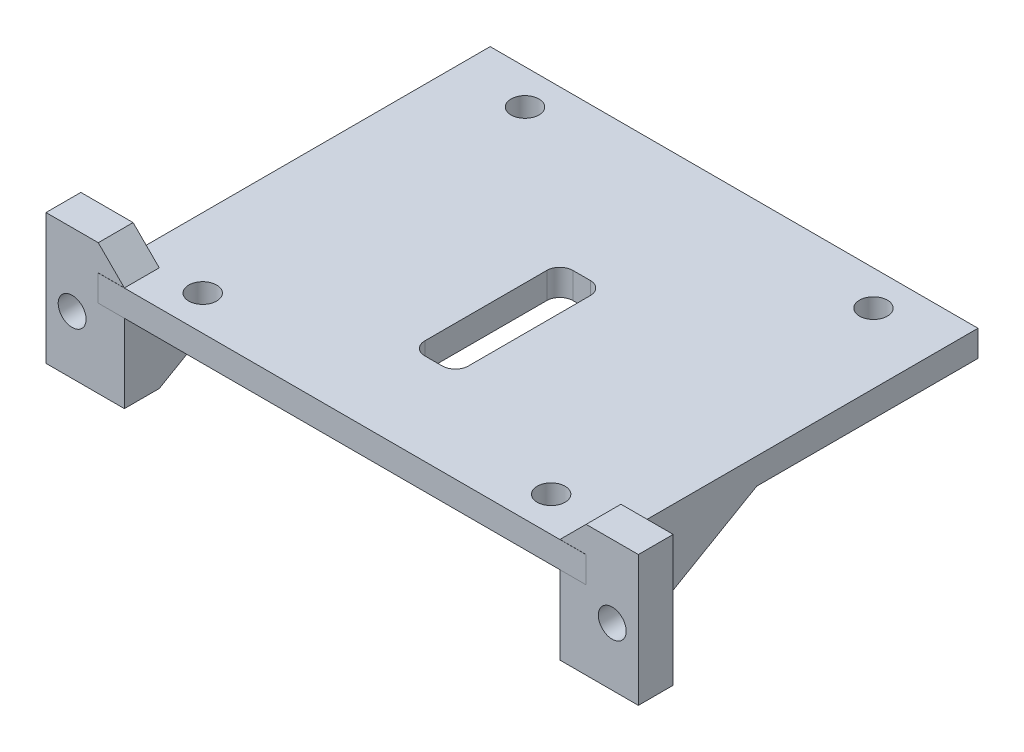
SolidWorks part; units mm, degrees
ref_plane "前视基准面" through (0, 0, 0) normal (0, 0, 1) x (1, 0, 0)
ref_plane "上视基准面" through (0, 0, 0) normal (0, 1, 0) x (1, 0, 0)
ref_plane "右视基准面" through (0, 0, 0) normal (1, 0, 0) x (0, 0, -1)
sketch "草图1" plane through (0, 0, 0) normal (0, 1, 0) x (1, 0, 0)
  line L1 (0, 0) -> (56, 0)
  line L2 (0, 0) -> (0, 45)
  line L3 (0, 45) -> (56, 45)
  line L4 (56, 0) -> (56, 45)
  dimension "D1" = 45
  dimension "D2" = 56
extrude "凸台-拉伸1" add sketch "草图1" along normal blind 3
sketch "草图2" plane through (0, 0, 0) normal (-1, 0, 0) x (0, 0, 1)
  line L0 (-0.013, 6) -> (-4.013, 6)
  line L1 (-4.013, 6) -> (-4.013, -9)
  line L2 (-4.013, -9) -> (-0.013, -9)
  line L3 (-0.013, -9) -> (-0.013, 6)
  line L4 (-45, 3) -> (0, 3) construction
  line L5 (-45, 0) -> (0, 0) construction
  dimension "D1" = 3
  dimension "D2" = 9
  dimension "D3" = 4
extrude "凸台-拉伸2" add sketch "草图2" along normal blind 6
sketch "草图3" plane through (56, 0, 0) normal (1, 0, 0) x (0, 0, -1)
  line L0 (0.013, 6) -> (0.013, -9)
  line L1 (0.013, -9) -> (4.013, -9)
  line L2 (4.013, -9) -> (4.013, 6)
  line L3 (4.013, 6) -> (0.013, 6)
extrude "凸台-拉伸3" add sketch "草图3" along normal blind 6
sketch "草图4" plane through (56, 0, 0) normal (-1, 0, 0) x (0, 0, 1)
  line L0 (-4.013, -9) -> (-19.6015, 0)
  line L1 (-4.013, 0) -> (-45, 0) construction
  line L2 (-19.6015, 0) -> (-0.013, 0)
  line L3 (-0.013, 0) -> (-0.013, -9)
  line L4 (-0.013, -9) -> (-4.013, -9)
  dimension "D1" = 30
extrude "凸台-拉伸4" add sketch "草图4" along normal blind 3
sketch "草图5" plane through (0, 0, 0) normal (1, 0, 0) x (0, 0, -1)
  line L0 (0.013, 0.3045) -> (0.013, -9)
  line L1 (0.013, -9) -> (4.013, -9)
  line L2 (4.013, -9) -> (19.6015, 0)
  line L3 (45, 0) -> (4.013, 0) construction
  line L4 (19.6015, 0) -> (0, 0)
  line M3 (4.013, -9) -> (4.013, 0)
  line M4 (4.013, 0) -> (0.013, 0)
  line M5 (0.013, 0) -> (0.013, -9)
  line M6 (0.013, -9) -> (4.013, -9)
  dimension "D1" = 30
extrude "凸台-拉伸5" add sketch "草图5" along normal blind 3 contours L2 L4 M3 | M6 M3 M4 M5 region at (0, -4.5, -2.013) region at (0, -3, -9.2092)
chamfer "倒角1" distance 3 angle 45 2 edges at (0, 3, -2.013) (56, 3, -2.013)
sketch "草图6" plane through (0, 0, -4.013) normal (0, 0, -1) x (-1, 0, 0)
  line L0 (-59, -2.3233) -> (3, -2.3233) construction
  line L1 (-62, -9) -> (-62, 6) construction
  line L2 (6, 6) -> (6, -9) construction
  circle A0 centre (3, -2.3233) radius 1.6
  circle A1 centre (-59, -2.3233) radius 1.6
  dimension "D1" = 3
  dimension "D2" = 3
extrude "切除-拉伸1" cut sketch "草图6" against normal blind 4
sketch "草图7" plane through (0, 3, 0) normal (0, 1, 0) x (1, 0, 0)
  line L0 (28, 49.7957) -> (28, -5.721) construction
  line L1 (8, 41) -> (8, 4)
  line L2 (0, 0) -> (56, 0) construction
  line L3 (0, 45) -> (0, 4.013) construction
  line L4 (48, 41) -> (48, 4)
  circle A0 centre (8, 41) radius 1.6
  circle A1 centre (8, 4) radius 1.6
  circle A2 centre (48, 4) radius 1.6
  circle A3 centre (48, 41) radius 1.6
  dimension "D1" = 37
  dimension "D2" = 4
  dimension "D3" = 8
extrude "切除-拉伸2" cut sketch "草图7" against normal blind 3 contours A3 | A2 | A0 | A1 region at (49.0994, 3, -5.0994) region at (46.9006, 3, -42.0994)
sketch "草图8" plane through (0, 0, 0) normal (0, -1, 0) x (1, 0, 0)
  line L0 (24, -45) -> (32, -45)
  line L1 (56, -45) -> (0, -45) construction
  line L2 (32, -45) -> (32, -42)
  line L3 (32, -42) -> (24, -42)
  line L4 (24, -42) -> (24, -45)
  line L5 (28, 5.34) -> (28, -50.6665) construction
  line L6 (0, -45) -> (0, -19.6015) construction
  point P10 (32, -43.5)
  dimension "D1" = 28
  dimension "D2" = 3
  dimension "D3" = 8
  dimension "D4" = 4
extrude "凸台-拉伸6" add sketch "草图8" along normal blind 9
sketch "草图9" plane through (32, 0, 0) normal (1, 0, 0) x (0, 0, -1)
  line L0 (45, 0) -> (29.1467, 0)
  line L1 (29.1467, 0) -> (42, -9)
  line L2 (42, -9) -> (45, -9)
  line L3 (45, -9) -> (45, 0)
  dimension "D1" = 35
extrude "凸台-拉伸7" add sketch "草图9" along normal blind 3
sketch "草图10" plane through (24, 0, 0) normal (-1, 0, 0) x (0, 0, 1)
  line L0 (-45, 0) -> (-45, -9)
  line L1 (-45, -9) -> (-42, -9)
  line L2 (-42, -9) -> (-29.1467, 0)
  line L3 (-29.1467, 0) -> (-45, 0)
extrude "凸台-拉伸8" add sketch "草图10" along normal blind 3
sketch "草图11" plane through (0, 0, -42) normal (0, 0, 1) x (1, 0, 0)
  line L0 (24, -9) -> (24, 0) construction
  line L1 (32, -9) -> (24, -9) construction
  circle A0 centre (28, -4.5) radius 1.6
  dimension "D1" = 4
  dimension "D2" = 4.5
extrude "切除-拉伸3" cut sketch "草图11" against normal blind 3
sketch "草图12" plane through (0, 3, 0) normal (0, 1, 0) x (1, 0, 0)
  line L0 (28, 49.4691) -> (28, -3.816) construction
  line L1 (25.5, 27.5) -> (25.5, 10.5)
  line L2 (25.5, 10.5) -> (30.5, 10.5)
  line L3 (30.5, 10.5) -> (30.5, 27.5)
  line L4 (30.5, 27.5) -> (25.5, 27.5)
  line L5 (0, 45) -> (0, 4.013) construction
  line L6 (-5.009, 22.5) -> (59.3487, 22.5) construction
  line L7 (0, 0) -> (56, 0) construction
  dimension "D1" = 28
  dimension "D2" = 2.5
  dimension "D3" = 2.5
  dimension "D4" = 22.5
  dimension "D5" = 5
  dimension "D6" = 12
extrude "切除-拉伸4" cut sketch "草图12" against normal blind 3
fillet "圆角1" radius 1.5 4 edges at (30.5, 1.5, -10.5) (25.5, 1.5, -10.5) (25.5, 1.5, -27.5) (30.5, 1.5, -27.5)
